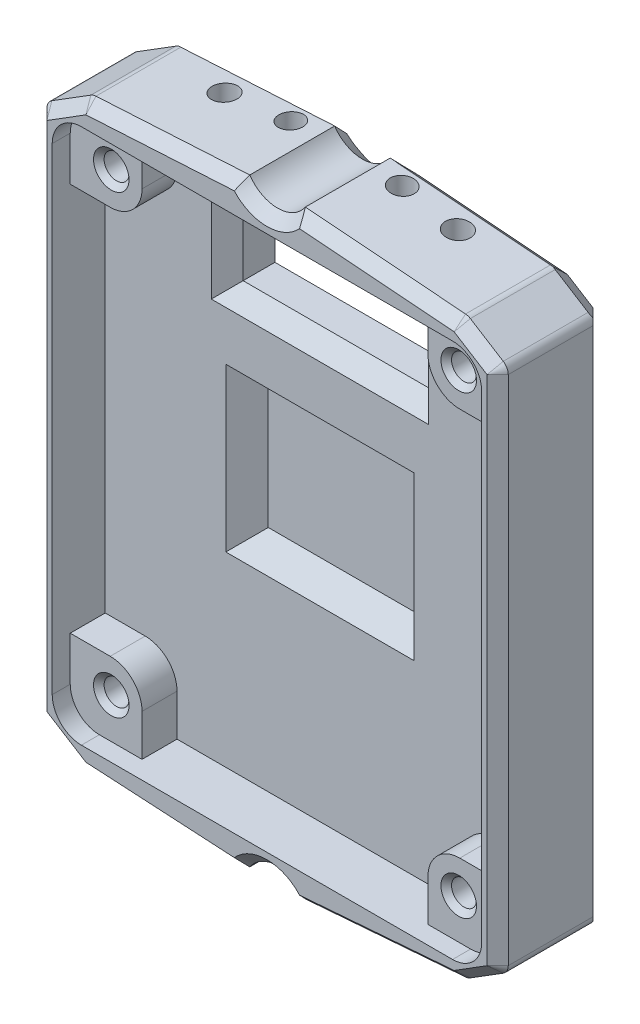
SolidWorks part; units mm, degrees
other "Markup1"
sketch "Sketch12" plane through (21.7503, 28.25, -6.4365) normal (0.888, 0.078, -0.4531) x (-0.4517, -0.0362, -0.8914)
ref_plane "Front Plane" through (0, 0, 0) normal (0, 0, 1) x (1, 0, 0)
ref_plane "Top Plane" through (0, 0, 0) normal (0, 1, 0) x (1, 0, 0)
ref_plane "Right Plane" through (0, 0, 0) normal (1, 0, 0) x (0, 0, -1)
sketch "Sketch1" plane through (0, 0, 0) normal (0, 0, 1) x (1, 0, 0)
  line L0 (-23.25, 28.25) -> (-23.25, -28.25)
  line L1 (-20.25, 25.25) -> (20.25, 25.25)
  line L2 (-20.25, 25.25) -> (-20.25, -25.25)
  line L3 (-20.25, -25.25) -> (20.25, -25.25)
  line L4 (20.25, 25.25) -> (20.25, -25.25)
  line L5 (-20.25, 25.25) -> (20.25, -25.25) construction
  line L6 (-20.25, -25.25) -> (20.25, 25.25) construction
  line L7 (-23.25, -28.25) -> (23.25, -28.25)
  line L8 (23.25, 28.25) -> (23.25, -28.25)
  line L9 (-23.25, 28.25) -> (23.25, 28.25)
  point P0 (0, 0)
  dimension "D1" = 50.5
  dimension "D2" = 40.5
  dimension "D3" = 3
extrude "Boss-Extrude1" add sketch "Sketch1" along normal blind 5
sketch "Sketch2" plane through (0, 0, 0) normal (0, 0, -1) x (-1, 0, 0)
  line L1 (-23.25, 28.25) -> (23.25, 28.25)
  line L2 (-23.25, 28.25) -> (-23.25, -28.25)
  line L3 (-23.25, -28.25) -> (23.25, -28.25)
  line L4 (23.25, 28.25) -> (23.25, -28.25)
extrude "Boss-Extrude2" add sketch "Sketch2" along normal blind 6
sketch "Sketch3" plane through (0, 0, 0) normal (0, 0, 1) x (1, 0, 0)
  line L0 (0, 0) -> (0, 30.8352) construction
  line L1 (0, 0) -> (-31.9704, 0) construction
  line L2 (-20.25, 25.25) -> (-20.25, 18.3322)
  line L3 (-20.25, 25.25) -> (-20.25, -25.25) construction
  line L4 (-20.25, 18.3322) -> (-13.4806, 18.3322)
  line L5 (-13.4806, 18.3322) -> (-13.4806, 25.25)
  line L6 (20.25, 25.25) -> (-20.25, 25.25) construction
  line L7 (-13.4806, 25.25) -> (-20.25, 25.25)
  line L8 (13.4806, 25.25) -> (20.25, 25.25)
  line L9 (13.4806, 18.3322) -> (13.4806, 25.25)
  line L10 (20.25, 18.3322) -> (13.4806, 18.3322)
  line L11 (20.25, 25.25) -> (20.25, 18.3322)
  line L12 (20.25, -25.25) -> (20.25, -18.3322)
  line L13 (20.25, -18.3322) -> (13.4806, -18.3322)
  line L14 (13.4806, -18.3322) -> (13.4806, -25.25)
  line L15 (13.4806, -25.25) -> (20.25, -25.25)
  line L16 (-13.4806, -25.25) -> (-20.25, -25.25)
  line L17 (-13.4806, -18.3322) -> (-13.4806, -25.25)
  line L18 (-20.25, -18.3322) -> (-13.4806, -18.3322)
  line L19 (-20.25, -25.25) -> (-20.25, -18.3322)
  circle A0 centre (-16.38, 21.46) radius 1.175
  circle A1 centre (16.38, 21.46) radius 1.175
  circle A2 centre (16.38, -21.46) radius 1.175
  circle A3 centre (-16.38, -21.46) radius 1.175
  dimension "D3" = 2.35
  dimension "D1" = 21.46
  dimension "D2" = 16.38
extrude "Boss-Extrude3" add sketch "Sketch3" along normal blind 3.3
chamfer "Chamfer3" distance 4.5 angle 58 4 edges at (-23.25, -28.25, -0.5) (23.25, -28.25, -0.5) (-23.25, 28.25, -0.5) (23.25, 28.25, -0.5) first distance on face at (-23.25, 0, -0.5) first distance on face at (23.25, 0, -0.5)
fillet "Fillet1" radius 3 4 edges at (13.4806, -18.3322, 1.65) (-13.4806, -18.3322, 1.65) (13.4806, 18.3322, 1.65) (-13.4806, 18.3322, 1.65)
sketch "Sketch4" plane through (0, 0, 0) normal (0, 0, 1) x (1, 0, 0)
  line L0 (20.25, 25.25) -> (-20.25, 25.25) construction
  line L1 (-8.75, 23.8) -> (8.75, 23.8)
  line L2 (-8.75, 23.8) -> (-8.75, 13.8)
  line L3 (-8.75, 13.8) -> (8.75, 13.8)
  line L4 (8.75, 23.8) -> (8.75, 13.8)
  point P4 (0, 13.8)
  dimension "D1" = 10
  dimension "D2" = 1.45
  dimension "D3" = 17.5
extrude "Cut-Extrude1" cut sketch "Sketch4" against normal through all
sketch "Sketch5" plane through (0, 0, -6) normal (0, 0, -1) x (-1, 0, 0)
  line L0 (-29.5901, 0) -> (35.962, 0) construction
  line L4 (0, 42.4173) -> (0, 14.6256) construction
  line L8 (-23.25, -28.25) -> (23.25, -28.25)
  line L9 (23.25, -28.25) -> (23.25, -27.0847)
  line L10 (23.25, -27.0847) -> (2.6192, -28.25)
  line L11 (-23.25, -26.638) -> (-2.6192, -28.25)
  line L12 (-23.25, -28.25) -> (-23.25, -26.638)
  line L14 (16.0485, 28.25) -> (-16.0485, 28.25) construction
  line L15 (-2.6192, 28.25) -> (2.6192, 28.25)
  line L16 (-23.25, 28.25) -> (-23.25, 26.638)
  line L17 (-23.25, 26.638) -> (-2.6192, 28.25)
  line L18 (23.25, 27.0847) -> (2.6192, 28.25)
  line L19 (23.25, 28.25) -> (23.25, 27.0847)
  line L20 (-23.25, 28.25) -> (23.25, 28.25)
  arc A0 (-2.6192, 28.25) -> (2.6192, 28.25) centre (0, 30) ccw
  arc A1 (-2.6192, -28.25) -> (2.6192, -28.25) centre (0, -30) cw
  line M10 (-16.0485, -28.25) -> (16.0485, -28.25)
  line M12 (16.0485, 28.25) -> (-16.0485, 28.25)
  line M22 (16.0485, -28.25) -> (23.25, -23.75)
  line M23 (23.25, 23.75) -> (16.0485, 28.25)
  line M24 (-16.0485, 28.25) -> (-23.25, 23.75)
  line M25 (-23.25, -23.75) -> (-16.0485, -28.25)
  dimension "D1" = 6.3
  dimension "D3" = 60
extrude "Cut-Extrude2" cut sketch "Sketch5" against normal through all contours L12 L8 L11 M25 | A1 L8 | L9 L10 L8 M22 | L11 M25 M10 | L10 L8 M22 | L17 M24 M12 | L18 M23 M12 | L20 L18 L19 M23 | L20 L16 L17 M24 | A0 M12 | L11 A1 L10 L9 L8 L12 region at (20.2805, -27.5835, -6) region at (-12.0169, -27.972, -6) region at (0, -27.6777, -6) region at (12.2118, -27.8502, -6) region at (-20.1718, -27.7652, -6) region at (-12.0169, 27.972, -6) region at (12.2118, 27.8502, -6) region at (0, 27.6777, -6) region at (20.2805, 27.5835, -6) region at (-20.1718, 27.7652, -6)
sketch "Sketch6" plane through (0, 0, 5) normal (0, 0, 1) x (1, 0, 0)
  line L0 (-17.3831, -27.4161) -> (-2.6192, -28.25) construction
  line L1 (-23.2503, 33.2078) -> (-21.7503, 33.2078)
  line L2 (-23.2503, 33.2078) -> (-23.2503, -27.1694)
  line L3 (-23.2503, -27.1694) -> (-21.7503, -27.1694)
  line L4 (-21.7503, 33.2078) -> (-21.7503, -27.1694)
  line L5 (0, 0) -> (0, 31.5361) construction
  line L6 (21.7503, 33.2078) -> (21.7503, -27.1694)
  line L7 (23.2503, -27.1694) -> (21.7503, -27.1694)
  line L8 (23.2503, 33.2078) -> (23.2503, -27.1694)
  line L9 (23.2503, 33.2078) -> (21.7503, 33.2078)
  dimension "D1" = 1.5
extrude "Cut-Extrude3" cut sketch "Sketch6" against normal through all
sketch "Sketch7" plane through (0, 0, 0) normal (0, 1, 0) x (1, 0, 0)
  line L0 (-5.25, 2.5) -> (5.25, 2.5) construction
  line L1 (2.6192, 6) -> (-2.6192, 6) construction
  circle A0 centre (-5.25, 2.5) radius 1.125
  circle A1 centre (5.25, 2.5) radius 1.125
  point P4 (0, 2.5)
  dimension "D1" = 2.25
  dimension "D2" = 10.5
  dimension "D3" = 3.5
extrude "Cut-Extrude4" cut sketch "Sketch7" against normal blind 10 from offset 30
mirror "Mirror1" about plane through (0, 0, 0) normal (0, 1, 0) of "Cut-Extrude4"
chamfer "Chamfer6" distance 2 angle 45 12 edges at (19.859, -25.8689, -6) (10.2934, -27.6504, -6) (0, -26.85, -6) (-10.0011, -27.833, -6) (-19.5667, -26.0516, -6) (-21.7503, 0, -6) (-19.5667, 26.0516, -6) (21.7503, 0, -6) (19.859, 25.8689, -6) (-10.0011, 27.833, -6) (0, 26.85, -6) (10.2934, 27.6504, -6)
fillet "Fillet2" radius 1 8 edges at (21.7503, -24.6871, 0.5) (17.9677, -27.0507, 0.5) (-17.3831, -27.4161, 0.5) (-21.7503, -24.6871, 0.5) (-21.7503, 24.6871, 0.5) (21.7503, 24.6871, 0.5) (-17.3831, 27.4161, 0.5) (17.9677, 27.0507, 0.5)
chamfer "Chamfer1" distance 1 angle 45 20 edges at (0, -26.85, 5) (0, 26.85, 5) (-9.8731, -27.8403, 5) (-21.7503, 0, 5) (10.1713, -27.6599, 5) (21.7503, 0, 5) (-17.3733, -27.3852, 5) (-19.4404, -26.1305, 5) (-19.4404, 26.1305, 5) (-21.6249, -24.6176, 5) (-21.6249, 24.6176, 5) (17.9585, -27.0226, 5) (19.7279, 25.9509, 5) (19.7279, -25.9509, 5) (21.6249, 24.6176, 5) (21.6249, -24.6176, 5) (-9.8731, 27.8403, 5) (-17.3733, 27.3852, 5) (10.1713, 27.6599, 5) (17.9585, 27.0226, 5)
fillet "Fillet3" radius 2.75 4 edges at (-20.25, -25.25, 3.8088) (20.25, -25.25, 3.8088) (20.25, 25.25, 3.8088) (-20.25, 25.25, 3.8088)
sketch "Sketch8" plane through (0, 0, 3.3) normal (0, 0, 1) x (1, 0, 0)
  circle A0 centre (-16.38, 21.46) radius 1.175
  circle A1 centre (16.38, 21.46) radius 1.175
  circle A2 centre (16.38, -21.46) radius 1.175
  circle A3 centre (-16.38, -21.46) radius 1.175
  circle A4 centre (-16.38, 21.46) radius 1.175 construction
extrude "Cut-Extrude5" cut sketch "Sketch8" against normal through all
sketch "Sketch9" plane through (0, 0, -6) normal (0, 0, -1) x (-1, 0, 0)
  line L0 (0, 9.9819) -> (0, -23.9909) construction
  line L1 (-16.3742, -2.0365) -> (-6.3848, -2.0365)
  line L2 (-12.6187, -3.5365) -> (-6.3848, -3.5365)
  line L3 (-16.3742, -2.0365) -> (0, -17.5995)
  line L4 (-12.6187, -3.5365) -> (0, -15.5301)
  line L5 (-4, -2.7865) -> (-12.6323, -2.7865) construction
  line L6 (12.6187, -3.5365) -> (0, -15.5301)
  line L7 (16.3742, -2.0365) -> (0, -17.5995)
  line L8 (12.6187, -3.5365) -> (6.3848, -3.5365)
  line L9 (16.3742, -2.0365) -> (6.3848, -2.0365)
  arc A0 (-6.3848, -3.5365) -> (-6.3848, -2.0365) centre (-4, -2.7865) ccw
  arc A1 (6.3848, -3.5365) -> (6.3848, -2.0365) centre (4, -2.7865) cw
  dimension "D1" = 5
  dimension "D2" = 1.5
  dimension "D3" = 1.5
  dimension "D4" = 8
extrude "Cut-Extrude6" cut sketch "Sketch9" against normal blind 1
chamfer "Chamfer2" distance 0.5 angle 45 4 edges at (-17.555, -21.46, 3.3) (17.555, -21.46, 3.3) (15.205, 21.46, 3.3) (-15.205, 21.46, 3.3)
chamfer "Chamfer4" distance 1 angle 45 10 edges at (-8.1871, -9.818, -6) (-11.3795, -2.0365, -6) (-1.5, -2.7865, -6) (-9.5018, -3.5365, -6) (-6.3093, -9.5333, -6) (6.3093, -9.5333, -6) (9.5018, -3.5365, -6) (1.5, -2.7865, -6) (11.3795, -2.0365, -6) (8.1871, -9.818, -6)
sketch "Sketch10" plane through (0, 0, 0) normal (0, 1, 0) x (1, 0, 0)
  line L0 (-11, 2) -> (11, 2) construction
  circle A0 centre (-11, 2) radius 1.175
  circle A1 centre (11, 2) radius 1.175
  point P4 (0, 2)
  dimension "D1" = 2.35
  dimension "D2" = 22
  dimension "D3" = 2
extrude "Cut-Extrude7" cut sketch "Sketch10" against normal through all both and the other way through all
sketch "Sketch11" plane through (0, 0, 0) normal (0, 0, 1) x (1, 0, 0)
  line L1 (-8.8805, 7.6666) -> (8.8805, 7.6666)
  line L2 (-8.8805, 7.6666) -> (-8.8805, -7.6666)
  line L3 (-8.8805, -7.6666) -> (8.8805, -7.6666)
  line L4 (8.8805, 7.6666) -> (8.8805, -7.6666)
  line L5 (-8.8805, 7.6666) -> (8.8805, -7.6666) construction
  line L6 (-8.8805, -7.6666) -> (8.8805, 7.6666) construction
  point P0 (0, 0)
extrude "Cut-Extrude8" cut sketch "Sketch11" against normal blind 2
chamfer "Chamfer5" distance 2 angle 45 4 edges at (0, -7.6666, -2) (-8.8805, 0, -2) (0, 7.6666, -2) (8.8805, 0, -2)
chamfer "Chamfer7" distance 1.5 angle 45 8 edges at (8.75, 18.8, 0) (0, 23.8, 0) (-8.75, 18.8, 0) (0, 13.8, 0) (-8.75, 18.8, -6) (0, 23.8, -6) (8.75, 18.8, -6) (0, 13.8, -6)
